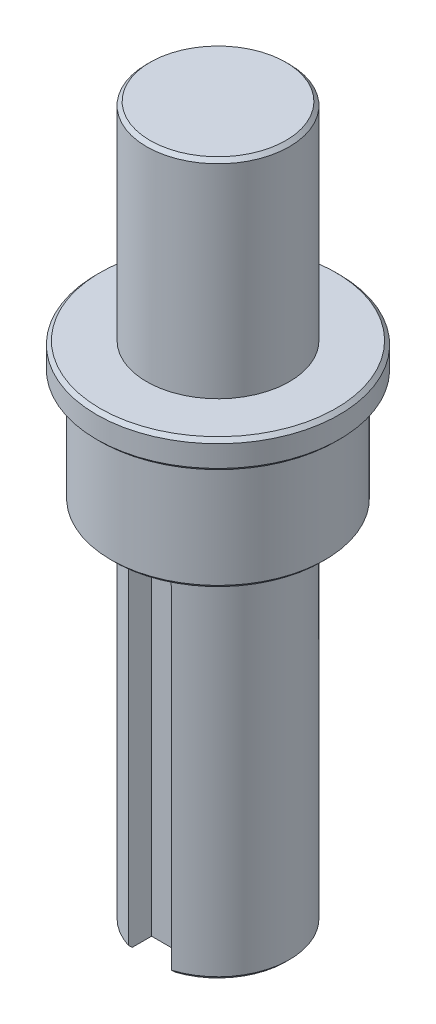
SolidWorks part; units mm, degrees
material "Chrome Stainless Steel"
ref_plane "Plan de face" through (0, 0, 0) normal (0, 0, 1) x (1, 0, 0)
ref_plane "Plan de dessus" through (0, 0, 0) normal (0, 1, 0) x (1, 0, 0)
ref_plane "Plan de droite" through (0, 0, 0) normal (1, 0, 0) x (0, 0, -1)
sketch "Sketch1" plane through (0, 0, 0) normal (0, 0, 1) x (1, 0, 0)
  line L0 (0, 0) -> (0, 74.3112) construction
  line L1 (0, 55.3656) -> (5, 55.3656)
  line L2 (5, 55.3656) -> (5, 40.8656)
  line L3 (5, 40.8656) -> (8.5, 40.8656)
  line L4 (8.5, 40.8656) -> (8.5, 38.8656)
  line L5 (8.5, 38.8656) -> (7.5, 38.8656)
  line L6 (7.5, 38.8656) -> (7.5, 31.0656)
  line L7 (7.5, 31.0656) -> (5, 31.0656)
  line L8 (5, 31.0656) -> (5, 5.5656)
  line L9 (5, 5.5656) -> (0, 5.5656)
  line L10 (0, 55.3656) -> (0, 5.5656)
  dimension "D1" = 5
  dimension "D2" = 17
  dimension "D3" = 15
  dimension "D4" = 14.5
  dimension "D5" = 2
  dimension "D6" = 7.8
  dimension "D7" = 25.5
  dimension "D8" = 10
revolve "Revolve1" add sketch "Sketch1" angle 360 about L0
hole_wizard "Tap Drill for M4 Tap1" positions "Sketch2" profile "Sketch3" hole size "M4" standard "ISO"
sketch "Sketch2" plane through (0, 5.5656, 0) normal (0, -1, 0) x (-1, 0, 0)
  point P0 (0, 0)
sketch "Sketch3" plane through (0, 5.5656, 0) normal (1, 0, 0) x (0, 0, -1)
  line L0 (0, 0) -> (0, 10.9914)
  line L1 (0, 10.9914) -> (1.65, 10)
  line L2 (1.65, 10) -> (1.65, 0)
  line L5 (1.65, 0) -> (0, 0)
  line L10 (0, 10.9914) -> (-1.65, 10) construction
  line L11 (0, -6.35) -> (0, 107.95) construction
  dimension "Hole Dia." = 3.3
  dimension "Hole Depth" = 10
  dimension "Drill Angle" = 118
chamfer "Chamfer1" distance 0.25 angle 45 6 edges at (0, 55.3656, -5) (0, 5.5656, -5) (0, 5.5656, -1.65) (0, 31.0656, -7.5) (0, 38.8656, -8.5) (0, 40.8656, -8.5)
sketch "Sketch4" plane through (0, 5.5656, 0) normal (0, -1, 0) x (1, 0, 0)
  line L1 (-1.5, 6.15) -> (1.5, 6.15)
  line L2 (-1.5, 6.15) -> (-1.5, 3.15)
  line L3 (-1.5, 3.15) -> (1.5, 3.15)
  line L4 (1.5, 6.15) -> (1.5, 3.15)
  circle A0 centre (0, 0) radius 5 construction
  dimension "D1" = 3
  dimension "D2" = 3
  dimension "D3" = 3.15
  dimension "D4" = 1.5
extrude "Cut-Extrude1" cut sketch "Sketch4" against normal blind 25
fillet "Fillet1" radius 1.5 2 edges at (1.5, 30.5656, 3.9598) (-1.5, 30.5656, 3.9598)
